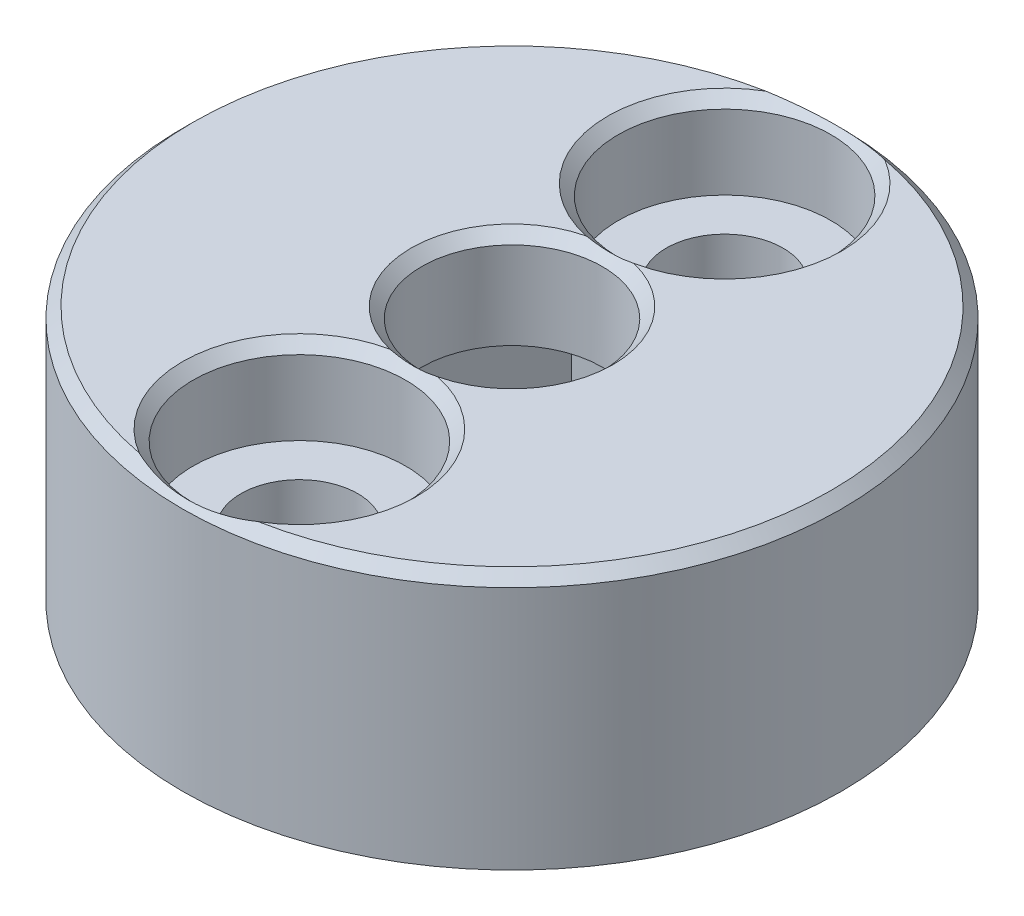
SolidWorks part; units mm, degrees
ref_plane "Front Plane" through (0, 0, 0) normal (0, 0, 1) x (1, 0, 0)
ref_plane "Top Plane" through (0, 0, 0) normal (0, 1, 0) x (1, 0, 0)
ref_plane "Right Plane" through (0, 0, 0) normal (1, 0, 0) x (0, 0, -1)
sketch "Sketch1" plane through (0, 0, 0) normal (0, 1, 0) x (1, 0, 0)
  circle A0 centre (0, 0) radius 15.5
  dimension "D1" = 31
extrude "Boss-Extrude1" add sketch "Sketch1" along normal blind 12
sketch "Sketch2" plane through (0, 12, 0) normal (0, 1, 0) x (1, 0, 0)
  circle A0 centre (0, 0) radius 10 construction
  circle A1 centre (0, 10) radius 2.75
  circle A2 centre (0, -10) radius 2.75
  point P12 (0, 0)
  dimension "D1" = 20
  dimension "D3" = 5.5
  dimension "D2" = 2
extrude "Cut-Extrude1" cut sketch "Sketch2" against normal through all
sketch "Sketch3" plane through (0, 12, 0) normal (0, 1, 0) x (1, 0, 0)
  circle A0 centre (0, 0) radius 4.25
  dimension "D1" = 8.5
extrude "Cut-Extrude2" cut sketch "Sketch3" against normal through all
sketch "Sketch4" plane through (0, 0, 0) normal (0, -1, 0) x (1, 0, 0)
  line L1 (3.7989, -6.54) -> (7.5633, 0.02)
  line L2 (7.5633, 0.02) -> (3.7643, 6.56)
  line L3 (3.7643, 6.56) -> (-3.7989, 6.54)
  line L4 (-3.7989, 6.54) -> (-7.5633, -0.02)
  line L5 (-7.5633, -0.02) -> (-3.7643, -6.56)
  line L6 (-3.7643, -6.56) -> (3.7989, -6.54)
  circle A0 centre (0, 0) radius 6.55 construction
  dimension "D1" = 13.1
extrude "Cut-Extrude3" cut sketch "Sketch4" against normal blind 7.4
sketch "Sketch5" plane through (0, 12, 0) normal (0, 1, 0) x (1, 0, 0)
  circle A0 centre (0, 10) radius 5
  circle A1 centre (0, -10) radius 5
  dimension "D1" = 10
extrude "Cut-Extrude4" cut sketch "Sketch5" against normal offset from surface (4 mm away) 8 up to face at (0, 0, 0)
chamfer "Chamfer1" distance 0.5 angle 45 4 edges at (0, 12, 15.5) (0, 12, 15) (0, 12, 4.25) (0, 12, -5)
equation "\"D1@Cut-Extrude3\"=6.40мм+1"
equation "\"D1@Cut-Extrude4\"=12-4"
